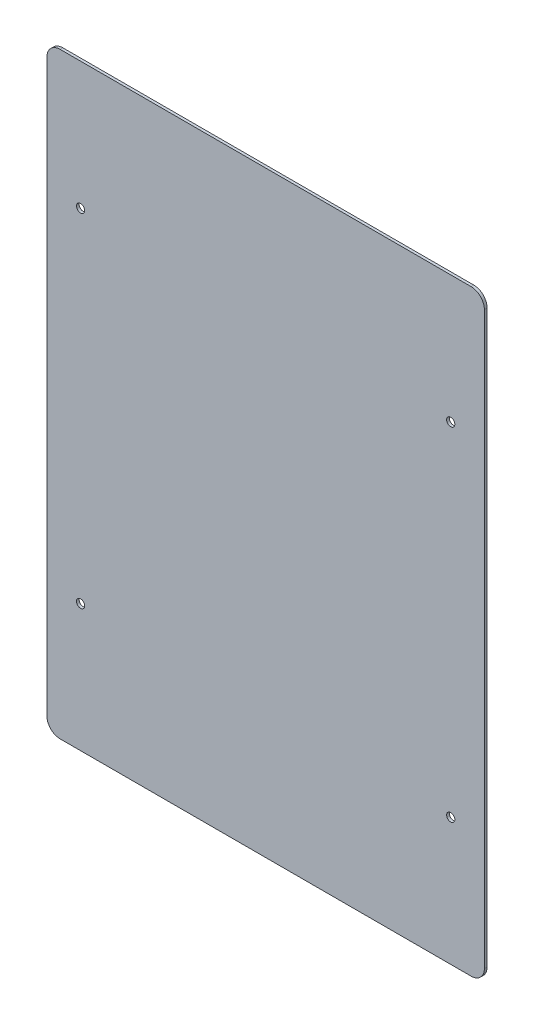
SolidWorks part; units mm, degrees
ref_plane "Front Plane" through (0, 0, 0) normal (0, 0, 1) x (1, 0, 0)
ref_plane "Top Plane" through (0, 0, 0) normal (0, 1, 0) x (1, 0, 0)
ref_plane "Right Plane" through (0, 0, 0) normal (1, 0, 0) x (0, 0, -1)
sketch "Sketch2" plane through (0, 0, 0) normal (0, 0, 1) x (1, 0, 0)
  line L1 (-165, 225.24) -> (165, 225.24)
  line L2 (-165, 225.24) -> (-165, -225.24)
  line L3 (-165, -225.24) -> (165, -225.24)
  line L4 (165, 225.24) -> (165, -225.24)
  line L5 (-165, 225.24) -> (165, -225.24) construction
  line L6 (-165, -225.24) -> (165, 225.24) construction
  point P0 (0, 0)
  dimension "Length 1" = 330
  dimension "Length 2" = 450.48
extrude "Boss-Extrude1" add sketch "Sketch2" along normal blind 2.032
sketch "Sketch3" [suppressed] plane through (0, 0, 2.032) normal (0, 0, 1) x (1, 0, 0)
  circle A0 centre (-175.117, 128.01) radius 3.1
  circle A1 centre (175.117, 128.01) radius 3.1
  circle A8 centre (-175.1171, -128.01) radius 3.1
  circle A9 centre (175.1169, -128.01) radius 3.1
  dimension "D1" = 6.2
extrude "Cut-Extrude1" [suppressed] cut sketch "Sketch3" against normal through all both and the other way through all
fillet "Fillet1" [suppressed] radius 10
sketch "Sketch4" [suppressed] plane through (0, 0, 0) normal (0, 0, -1) x (-1, 0, 0)
  circle A0 centre (-423.777, 128.01) radius 3.1
  circle A1 centre (423.777, 128.01) radius 3.1
  circle A2 centre (423.777, -128.01) radius 3.1
  circle A3 centre (-423.777, -128.01) radius 3.1
  dimension "D1" = 6.2
extrude "Cut-Extrude2" [suppressed] cut sketch "Sketch4" against normal through all both and the other way through all
fillet "Fillet2" [suppressed] radius 10
sketch "Sketch5" [suppressed] plane through (0, 0, 0) normal (0, 0, -1) x (-1, 0, 0)
  circle A0 centre (-175.117, -437.5) radius 3.1
  circle A1 centre (175.1169, -437.5) radius 3.1
  circle A2 centre (175.1169, 437.5) radius 3.1
  circle A3 centre (-175.117, 437.5) radius 3.1
  dimension "D1" = 6.2
extrude "Cut-Extrude3" [suppressed] cut sketch "Sketch5" against normal through all both and the other way through all
fillet "Fillet3" [suppressed] radius 10
sketch "Sketch6" [suppressed] plane through (0, 0, 0) normal (0, 0, -1) x (-1, 0, 0)
  circle A0 centre (175.9, -175.117) radius 3.1
  circle A1 centre (175.9, 175.117) radius 3.1
  circle A2 centre (-175.9, 175.117) radius 3.1
  circle A3 centre (-175.9, -175.117) radius 3.1
  dimension "D1" = 6.2
extrude "Cut-Extrude4" [suppressed] cut sketch "Sketch6" against normal through all both and the other way through all
sketch "Sketch7" plane through (0, 0, 2.032) normal (0, 0, 1) x (1, 0, 0)
  circle A0 centre (-139.6, -129.1099) radius 3.1
  circle A1 centre (-139.6, 129.11) radius 3.1
  circle A2 centre (139.6, 129.11) radius 3.1
  circle A3 centre (139.6, -129.1099) radius 3.1
  dimension "D1" = 6.2
extrude "Cut-Extrude5" cut sketch "Sketch7" against normal through all both and the other way through all
fillet "Fillet4" radius 10 4 edges at (-165, -225.24, 1.016) (165, -225.24, 1.016) (-165, 225.24, 1.016) (165, 225.24, 1.016)
